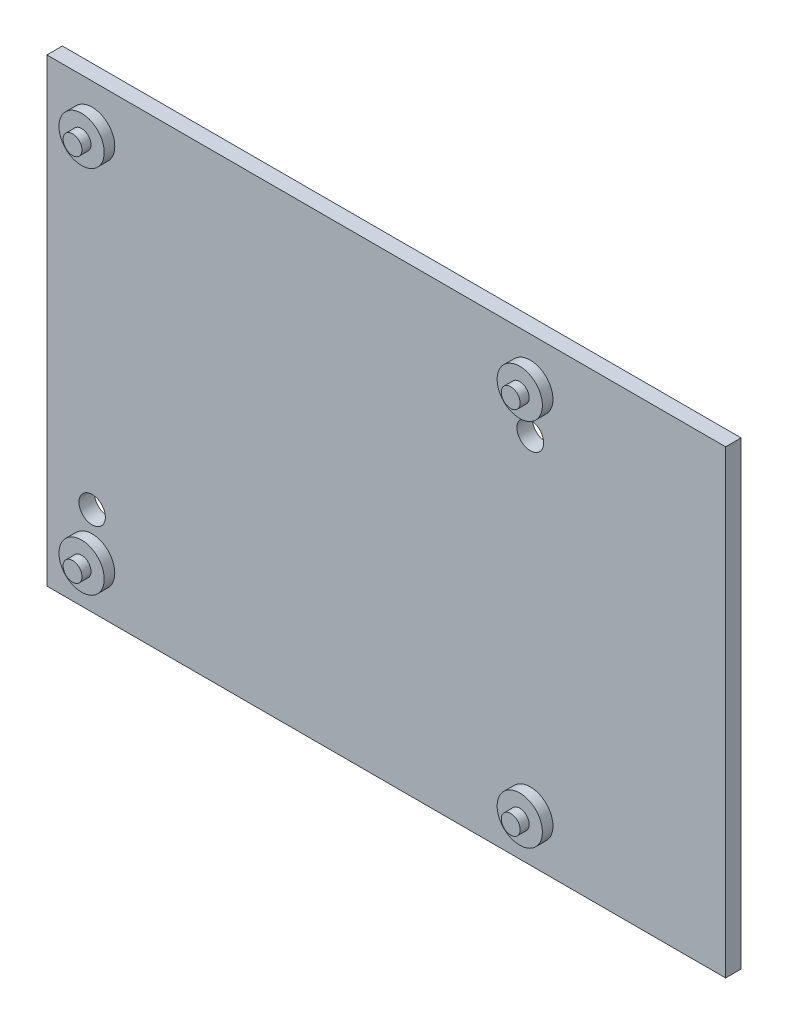
SolidWorks part; units mm, degrees
ref_plane "Front Plane" through (0, 0, 0) normal (0, 0, 1) x (1, 0, 0)
ref_plane "Top Plane" through (0, 0, 0) normal (0, 1, 0) x (1, 0, 0)
ref_plane "Right Plane" through (0, 0, 0) normal (1, 0, 0) x (0, 0, -1)
sketch "Base" plane through (0, 0, 0) normal (0, 0, 1) x (1, 0, 0)
  line L1 (-45, -30.5) -> (45, -30.5)
  line L2 (-45, -30.5) -> (-45, 30.5)
  line L3 (-45, 30.5) -> (45, 30.5)
  line L4 (45, -30.5) -> (45, 30.5)
  line L5 (-45, -30.5) -> (45, 30.5) construction
  line L6 (-45, 30.5) -> (45, -30.5) construction
  point P0 (0, 0)
  dimension "D1" = 90
  dimension "D2" = 61
sketch "Outer Pin" plane through (0, 0, 0) normal (0, 0, 1) x (1, 0, 0)
  line L0 (-45, 30.5) -> (-39, 30.5)
  line L1 (-45, 30.5) -> (45, 30.5) construction
  line L2 (-39, 30.5) -> (-39, 24.5)
  line L3 (-39, 24.5) -> (-39, -30.5)
  line L4 (-45, -30.5) -> (45, -30.5) construction
  line L5 (-39, -30.5) -> (-39, -24.5)
  line L6 (-45, -24.5) -> (19.1, -24.5)
  line L7 (-45, -30.5) -> (-45, 30.5) construction
  circle A0 centre (-39, 24.5) radius 3
  circle A1 centre (-39, -24.5) radius 3
  circle A2 centre (19.1, -24.5) radius 3
  circle A3 centre (19.1, 24.5) radius 3
  dimension "D1" = 6
  dimension "D2" = 6
  dimension "D3" = 6
  dimension "D4" = 6
extrude "Base Block" add sketch "Base" against normal blind 2.05
extrude "Outer Pin Stand" add sketch "Outer Pin" along normal blind 1.4 and the other way blind 0.5 separate body contours A0 | A1 | A2 | A3
sketch "Sketch3" plane through (0, 0, 0) normal (0, 0, 1) x (1, 0, 0)
  circle A0 centre (-39, 24.5) radius 1.25
  circle A1 centre (19.1, 24.5) radius 1.25
  circle A2 centre (19.1, -24.5) radius 1.25
  circle A3 centre (-39, -24.5) radius 1.25
  dimension "D1" = 2.5
  dimension "D2" = 2.5
  dimension "D3" = 2.5
  dimension "D4" = 2.5
extrude "Inner Pin Stand" add sketch "Sketch3" along normal blind 2.6 and the other way blind 0.5 separate body
sketch "Sketch5" plane through (0, 0, 0) normal (0, 0, 1) x (1, 0, 0)
  line L0 (-39, -24.5) -> (-39, -30.5)
  line L1 (-45, -30.5) -> (45, -30.5) construction
  line L2 (-39, -30.5) -> (-39, -18.72)
  line L3 (19.1, 24.5) -> (19.1, 18.8687)
  circle A0 centre (-39, -18.72) radius 1.75
  circle A1 centre (19.1, 18.8687) radius 1.775
  dimension "D1" = 3.5
  dimension "D2" = 3.55
extrude "Holes" add sketch "Sketch5" along normal blind 5 and the other way blind 5 separate body contours A0 | A1
combine bodies "Combine1" operation type add bodies to combine 101 102 109 105 110 104 111 103 106
combine bodies "Combine2" operation type subtract main body 112 bodies to subtract 108 107
